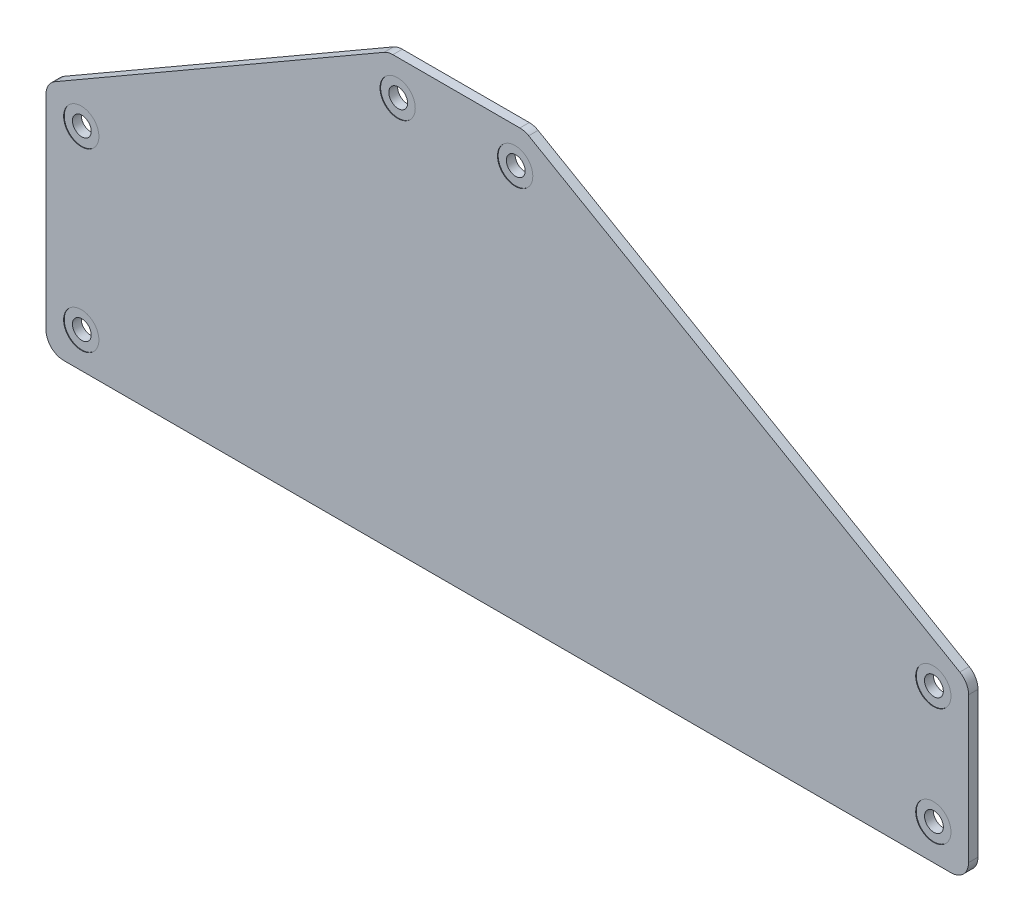
SolidWorks part; units mm, degrees
ref_plane "Front Plane" through (0, 0, 0) normal (0, 0, 1) x (1, 0, 0)
ref_plane "Top Plane" through (0, 0, 0) normal (0, 1, 0) x (1, 0, 0)
ref_plane "Right Plane" through (0, 0, 0) normal (1, 0, 0) x (0, 0, -1)
sketch "Sketch1" plane through (0, 0, 0) normal (0, 0, 1) x (1, 0, 0)
  line L0 (0, 0) -> (157, 0)
  line L1 (69.8397, 85.5596) -> (-55.1603, 13.3908) construction
  line L2 (-55.1603, 13.3908) -> (-55.1603, -130.9468) construction
  line L3 (-55.1603, -130.9468) -> (69.8397, -203.1155) construction
  line L4 (69.8397, -203.1155) -> (194.8397, -130.9468) construction
  line L5 (194.8397, -130.9468) -> (194.8397, 13.3908) construction
  line L6 (194.8397, 13.3908) -> (69.8397, 85.5596) construction
  line L7 (157, 0) -> (157, 29.4641)
  line L8 (157, 29.4641) -> (81.4474, 73.0844)
  line L9 (81.4474, 73.0844) -> (58.2321, 73.0844)
  line L10 (58.2321, 73.0844) -> (0, 39.4641)
  line L11 (0, 39.4641) -> (0, 0)
  line L12 (6, 36) -> (6, 6) construction
  line L13 (151, 26) -> (151, 6) construction
  line L14 (59.8397, 67.0844) -> (79.8397, 67.0844) construction
  line L15 (6, 6) -> (151, 6) construction
  line L16 (6, 6) -> (6, 0) construction
  line L17 (6, 6) -> (0, 6) construction
  line L18 (151, 6) -> (157, 6) construction
  line L19 (6, 36) -> (3, 41.1962) construction
  line L20 (151, 26) -> (154, 31.1962) construction
  line L21 (59.8397, 67.0844) -> (59.8397, 73.0844) construction
  line L22 (59.8397, 67.0844) -> (56.8397, 72.2805) construction
  line L23 (79.8397, 67.0844) -> (82.8397, 72.2805) construction
  line L24 (6, 36) -> (59.8397, 67.0844) construction
  line L25 (151, 26) -> (79.8397, 67.0844) construction
  circle A0 centre (69.8397, -58.778) radius 125 construction
  circle A1 centre (6, 36) radius 1.6
  circle A2 centre (6, 6) radius 1.6
  circle A3 centre (151, 6) radius 1.6
  circle A4 centre (151, 26) radius 1.6
  circle A5 centre (79.8397, 67.0844) radius 1.6
  circle A6 centre (59.8397, 67.0844) radius 1.6
  dimension "D9" = 3.2
  dimension "D1" = 250
  dimension "D2" = 5
  dimension "D3" = 5
  dimension "D4" = 20
  dimension "D5" = 145
  dimension "D6" = 20
  dimension "D7" = 6
  dimension "D8" = 30
extrude "Boss-Extrude1" add sketch "Sketch1" along normal blind 1.6
fillet "Fillet1" radius 3 6 edges at (0, 39.4641, 0.8) (58.2321, 73.0844, 0.8) (81.4474, 73.0844, 0.8) (157, 29.4641, 0.8) (157, 0, 0.8) (0, 0, 0.8)
sketch "Sketch2" plane through (0, 0, 1.6) normal (0, 0, 1) x (1, 0, 0)
  line L6 (57.5359, 72.6825) -> (1.5, 40.3301)
  line L7 (0, 37.7321) -> (0, 3)
  line L8 (3, 0) -> (154, 0)
  line L9 (157, 3) -> (157, 27.7321)
  line L10 (155.5, 30.3301) -> (82.1436, 72.6825)
  line L11 (80.6436, 73.0844) -> (59.0359, 73.0844)
  line L12 (57.5359, 72.6825) -> (1.5, 40.3301) construction
  line L13 (0, 37.7321) -> (0, 3) construction
  line L14 (3, 0) -> (154, 0) construction
  line L15 (157, 3) -> (157, 27.7321) construction
  line L16 (155.5, 30.3301) -> (82.1436, 72.6825) construction
  line L17 (80.6436, 73.0844) -> (59.0359, 73.0844) construction
  circle A0 centre (6, 6) radius 3
  circle A1 centre (6, 36) radius 3
  circle A2 centre (59.8397, 67.0844) radius 3
  circle A3 centre (79.8397, 67.0844) radius 3
  circle A4 centre (151, 26) radius 3
  circle A5 centre (151, 6) radius 3
  arc A6 (1.5, 40.3301) -> (0, 37.7321) centre (3, 37.7321) ccw
  arc A7 (0, 3) -> (3, 0) centre (3, 3) ccw
  arc A8 (154, 0) -> (157, 3) centre (154, 3) ccw
  arc A9 (157, 27.7321) -> (155.5, 30.3301) centre (154, 27.7321) ccw
  arc A10 (82.1436, 72.6825) -> (80.6436, 73.0844) centre (80.6436, 70.0844) ccw
  arc A11 (59.0359, 73.0844) -> (57.5359, 72.6825) centre (59.0359, 70.0844) ccw
  arc A12 (1.5, 40.3301) -> (0, 37.7321) centre (3, 37.7321) ccw construction
  arc A13 (0, 3) -> (3, 0) centre (3, 3) ccw construction
  arc A14 (154, 0) -> (157, 3) centre (154, 3) ccw construction
  arc A15 (157, 27.7321) -> (155.5, 30.3301) centre (154, 27.7321) ccw construction
  arc A16 (82.1436, 72.6825) -> (80.6436, 73.0844) centre (80.6436, 70.0844) ccw construction
  arc A17 (59.0359, 73.0844) -> (57.5359, 72.6825) centre (59.0359, 70.0844) ccw construction
  dimension "D2" = 6
  dimension "D1" = 0
extrude "Cut-Extrude1" cut sketch "Sketch2" against normal blind 0.1
